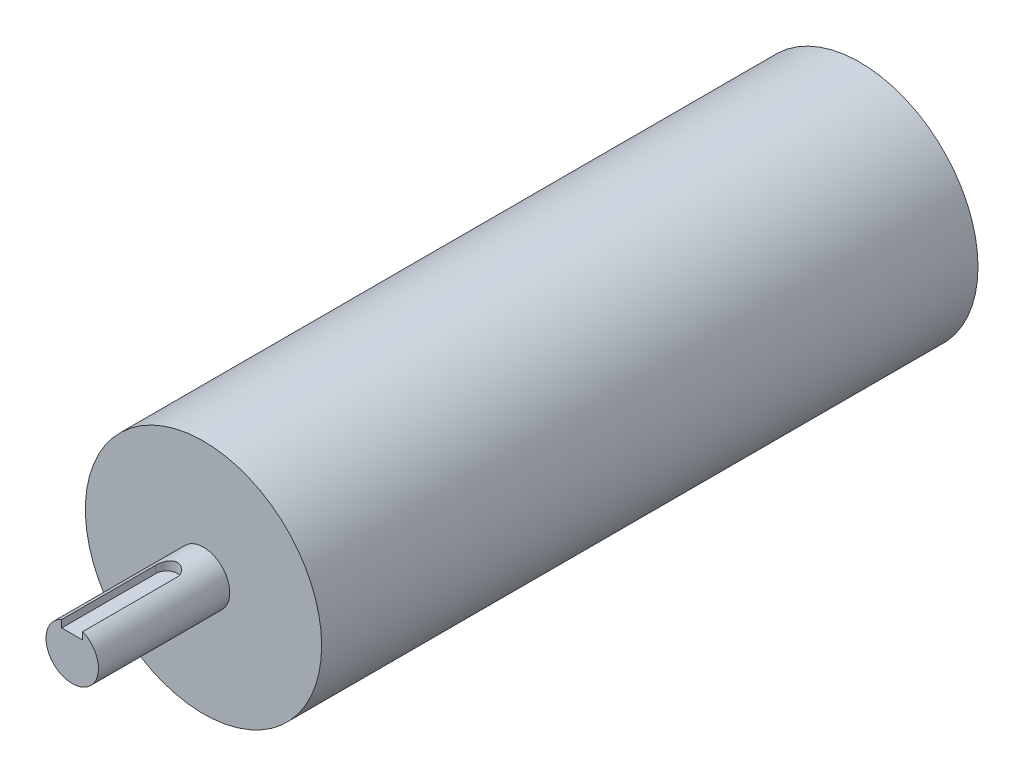
SolidWorks part; units mm, degrees
ref_plane "Front Plane" through (0, 0, 0) normal (0, 0, 1) x (1, 0, 0)
ref_plane "Top Plane" through (0, 0, 0) normal (0, 1, 0) x (1, 0, 0)
ref_plane "Right Plane" through (0, 0, 0) normal (1, 0, 0) x (0, 0, -1)
sketch "Sketch1" plane through (0, 0, 0) normal (0, 0, 1) x (1, 0, 0)
  circle A0 centre (0, 0) radius 22.5
  dimension "D1" = 45
extrude "Boss-Extrude1" add sketch "Sketch1" along normal blind 125
sketch "Sketch3" plane through (0, 0, 125) normal (0, 0, 1) x (1, 0, 0)
  line L1 (-5, 0) -> (5, 0) construction
  circle A0 centre (0, 0) radius 5
  dimension "D1" = 10
extrude "Boss-Extrude2" add sketch "Sketch3" along normal blind 25 contours L1 A0 | A0 L1 region at (0, 2.1221, 125) region at (0, -2.1221, 125)
sketch "Sketch4" plane through (0, 0, 150) normal (0, 0, 1) x (1, 0, 0)
  line L0 (0, 0) -> (5, 0) construction
  line L1 (-2, 3.185) -> (2, 3.185)
  line L2 (0, 0) -> (0, 5) construction
  line L3 (-2, 3.185) -> (-2, 4.5826)
  line L4 (2, 3.185) -> (2, 4.5826)
  circle A0 centre (0, 0) radius 5 construction
  circle A1 centre (0, 0) radius 5 construction
  arc A4 (2, 4.5826) -> (-2, 4.5826) centre (0, 0) ccw
  point P9 (0, 3.185)
  dimension "D1" = 4
  dimension "D2" = 1.815
extrude "Cut-Extrude1" cut sketch "Sketch4" against normal blind 20
fillet "Fillet1" 2 edges at (-2, 3.8838, 130) (2, 3.8838, 130) type full round first side face at (-2, 3.8838, 140) second side face at (2, 3.8838, 140) middle face at (0, 3.9881, 130)
